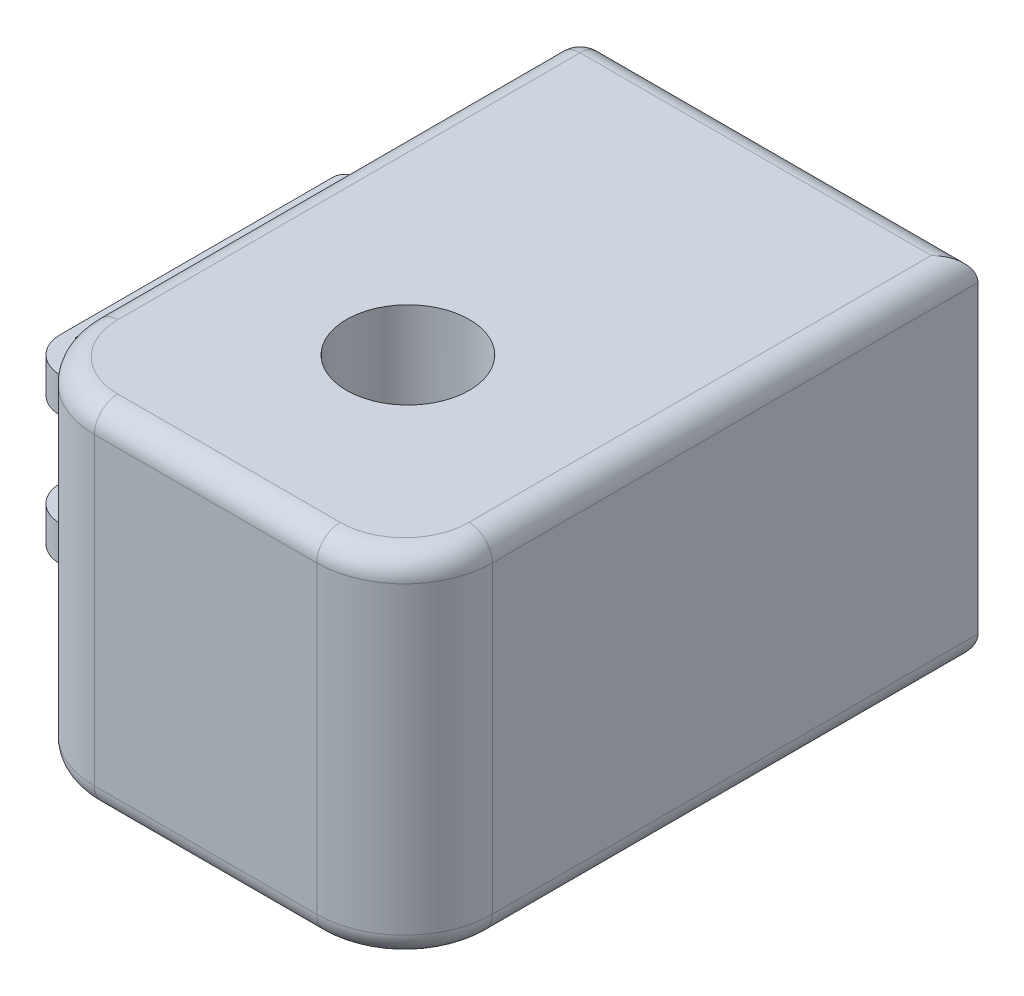
SolidWorks part; units mm, degrees
material "ABS"
ref_plane "Front Plane" through (0, 0, 0) normal (0, 0, 1) x (1, 0, 0)
ref_plane "Top Plane" through (0, 0, 0) normal (0, 1, 0) x (1, 0, 0)
ref_plane "Right Plane" through (0, 0, 0) normal (1, 0, 0) x (0, 0, -1)
sketch "Sketch1" plane through (0, 0, 0) normal (0, 0, 1) x (1, 0, 0)
  line L1 (17, -15) -> (-17, -15)
  line L2 (17, -15) -> (17, 15)
  line L3 (17, 15) -> (-17, 15)
  line L4 (-17, -15) -> (-17, 15)
  dimension "D1" = 34
  dimension "D2" = 30
  dimension "D3" = 15
  dimension "D4" = 17
extrude "Boss-Extrude1" add sketch "Sketch1" along normal blind 49
sketch "Sketch2" plane through (0, 0, 0) normal (0, 0, -1) x (-1, 0, 0)
  line L0 (-17, -15) -> (-17, 15) construction
  line L1 (17, -15) -> (-17, -15) construction
  circle A4 centre (-12, 9) radius 2 construction
  circle A5 centre (-12, -9) radius 2 construction
  circle A6 centre (12, -9) radius 2 construction
  circle A7 centre (12, 9) radius 2 construction
  circle A8 centre (12, -9) radius 2.1
  circle A9 centre (12, 9) radius 2.1
  circle A10 centre (-12, -9) radius 2.1
  circle A11 centre (-12, 9) radius 2.1
  dimension "D1" = 4
  dimension "D2" = 5
  dimension "D3" = 29
  dimension "D4" = 6
  dimension "D5" = 24
  dimension "D6" = 0.1
extrude "Cut-Extrude1" cut sketch "Sketch2" against normal blind 6
sketch "Sketch5" plane through (0, -15, 0) normal (0, -1, 0) x (1, 0, 0)
  line L0 (17, 49) -> (17, 0) construction
  line L2 (-17, 49) -> (17, 49) construction
  circle A1 centre (0, 31.7136) radius 11 construction
  circle A3 centre (0, 31.7136) radius 11.15
  dimension "D1" = 22
  dimension "D2" = 17
  dimension "D3" = 17.2864
  dimension "D4" = 0.15
extrude "Cut-Extrude2" cut sketch "Sketch5" against normal blind 12.5
sketch "Sketch6" plane through (0, 15, 0) normal (0, 1, 0) x (1, 0, 0)
  circle A1 centre (0, -31.7136) radius 5.1 construction
  circle A2 centre (0, -31.7136) radius 5.25
  dimension "D1" = 10.2
  dimension "D4" = 0.15
extrude "Cut-Extrude3" cut sketch "Sketch6" against normal blind 17.5
sketch "Sketch7" plane through (0, -2.5, 0) normal (0, -1, 0) x (1, 0, 0)
  circle A4 centre (7.9785, 31.127) radius 1.75 construction
  circle A5 centre (-0.5866, 39.6921) radius 1.75 construction
  circle A6 centre (-7.9785, 31.127) radius 1.75 construction
  circle A7 centre (0.5866, 23.7351) radius 1.75 construction
  circle A8 centre (-7.9785, 31.127) radius 2.1
  circle A9 centre (-0.5866, 39.6921) radius 2.1
  circle A10 centre (7.9785, 31.127) radius 2.1
  circle A11 centre (0.5866, 23.7351) radius 2.1
  circle A12 centre (0, 31.7136) radius 5.25 construction
  dimension "D2" = 4.2
  dimension "D3" = 0.5866
  dimension "D4" = 7.9785
  dimension "D5" = 0.5866
  dimension "D6" = 7.9785
  dimension "D7" = 0.5866
  dimension "D8" = 7.9785
  dimension "D9" = 0.5866
  dimension "D10" = 7.9785
  dimension "D1" = 0.35
extrude "Cut-Extrude4" cut sketch "Sketch7" against normal blind 6
chamfer "Chamfer1" distance 1 angle 45 4 edges at (7.9785, -2.5, 29.027) (-0.5866, -2.5, 37.5921) (-7.9785, -2.5, 29.027) (0.5866, -2.5, 21.6351)
chamfer "Chamfer2" distance 1 angle 45 4 edges at (9.9, -9, 0) (-14.1, -9, 0) (-14.1, 9, 0) (9.9, 9, 0)
fillet "Fillet1" radius 7.5 2 edges at (17, 0, 49) (-17, 0, 49)
fillet "Fillet2" radius 2 13 edges at (-17, 15, 20.75) (0, 15, 49) (0, -15, 49) (-17, -15, 20.75) (0, -15, 0) (-17, 0, 0) (0, 15, 0) (-14.8033, 15, 46.8033) (-14.8033, -15, 46.8033) (17, 15, 20.75) (14.8033, 15, 46.8033) (17, -15, 20.75) (14.8033, -15, 46.8033)
sketch "Sketch8" plane through (17, 0, 0) normal (1, 0, 0) x (0, 0, -1)
  line L1 (-42, 9) -> (-7, 9) construction
  line L2 (-42, 9) -> (-42, -9) construction
  line L3 (-42, -9) -> (-7, -9) construction
  line L4 (-7, 9) -> (-7, -9) construction
  line L5 (-42, 9) -> (-7, -9) construction
  line L6 (-42, -9) -> (-7, 9) construction
  line L7 (-47, 15) -> (-2, 15) construction
  circle A0 centre (-42, 9) radius 2.075
  circle A1 centre (-7, 9) radius 2.075
  circle A2 centre (-7, -9) radius 2.075
  circle A3 centre (-42, -9) radius 2.075
  point P0 (-24.5, 0)
  point P14 (-24.5, 15)
  dimension "D1" = 4.15
  dimension "D2" = 35
  dimension "D3" = 18
extrude "Cut-Extrude5" [suppressed] cut sketch "Sketch8" against normal blind 6.5
chamfer "Chamfer3" [suppressed] distance 1.5 angle 45
sketch "Sketch9" plane through (0, 0, 0) normal (0, 1, 0) x (1, 0, 0)
  line L0 (-17, -40.0491) -> (-24.3539, -40.0491)
  line L1 (-17, -2) -> (-17, -41.5) construction
  line L2 (-24.3539, -40.0491) -> (-24.3539, -12.7622)
  line L3 (-24.3539, -12.7622) -> (-17, -12.7622)
  line L4 (-17, -12.7622) -> (-17, -40.0491)
  line L5 (-20.6, -35) -> (-20.6, -19)
  circle A1 centre (-20.6, -35) radius 1.625
  circle A2 centre (-20.6, -19) radius 1.625
  dimension "D3" = 3.25
  dimension "D1" = 3.6
  dimension "D2" = 16
extrude "Boss-Extrude2" add sketch "Sketch9" along normal blind 3 from offset 4 contours L4 L3 L2 L0 A2 A1 region at (-20.6839, 0, 26.3521)
mirror "Mirror1" about plane through (0, 0, 0) normal (0, 1, 0) of "Boss-Extrude2"
fillet "Fillet3" radius 3 2 edges at (-24.3539, 5.5, 40.0491) (-24.3539, -5.5, 40.0491)
fillet "Fillet4" radius 1 4 edges at (-24.3539, 5.5, 12.7622) (-17, 5.5, 12.7622) (-17, -5.5, 12.7622) (-24.3539, -5.5, 12.7622)
sketch "Sketch10" plane through (0, 7, 0) normal (0, 1, 0) x (1, 0, 0)
  line L1 (-17.725, -20.6599) -> (-17.725, -17.3401)
  line L2 (-17.725, -17.3401) -> (-20.6, -15.6802)
  line L3 (-20.6, -15.6802) -> (-23.475, -17.3401)
  line L4 (-23.475, -17.3401) -> (-23.475, -20.6599)
  line L5 (-23.475, -20.6599) -> (-20.6, -22.3198)
  line L6 (-20.6, -22.3198) -> (-17.725, -20.6599)
  line L7 (-17.725, -36.6599) -> (-17.725, -33.3401)
  line L8 (-17.725, -33.3401) -> (-20.6, -31.6802)
  line L9 (-20.6, -31.6802) -> (-23.475, -33.3401)
  line L10 (-23.475, -33.3401) -> (-23.475, -36.6599)
  line L11 (-23.475, -36.6599) -> (-20.6, -38.3198)
  line L12 (-20.6, -38.3198) -> (-17.725, -36.6599)
  circle A0 centre (-20.6, -19) radius 2.875 construction
  circle A1 centre (-20.6, -35) radius 2.875 construction
  dimension "D1" = 5.75
extrude "Cut-Extrude6" cut sketch "Sketch10" against normal blind 2
ref_plane "Plane1" through (0, 0, 18.18) normal (0, 0, -1) x (-1, 0, 0)
sketch "Sketch13" plane through (0, -15, 0) normal (0, -1, 0) x (1, 0, 0)
  line L0 (-14.3, 18.18) -> (14.3, 18.18) construction
  line L1 (-10, 25.73) -> (10, 25.73) construction
  line L2 (-10, 25.73) -> (-10, 10.63) construction
  line L3 (-10, 10.63) -> (10, 10.63) construction
  line L4 (10, 25.73) -> (10, 10.63) construction
  line L5 (-15, 2) -> (15, 2) construction
  circle A0 centre (-10, 25.73) radius 2.05
  circle A1 centre (10, 25.73) radius 2.05
  circle A2 centre (-10, 10.63) radius 2.05
  circle A3 centre (10, 10.63) radius 2.05
  point P10 (10, 18.18)
  point P15 (0, 2)
  point P16 (0, 10.63)
  dimension "D1" = 4.1
  dimension "D2" = 5.5
  dimension "D3" = 20
extrude "Cut-Extrude7" [suppressed] cut sketch "Sketch13" against normal through all
chamfer "Chamfer4" [suppressed] distance 1 angle 45
